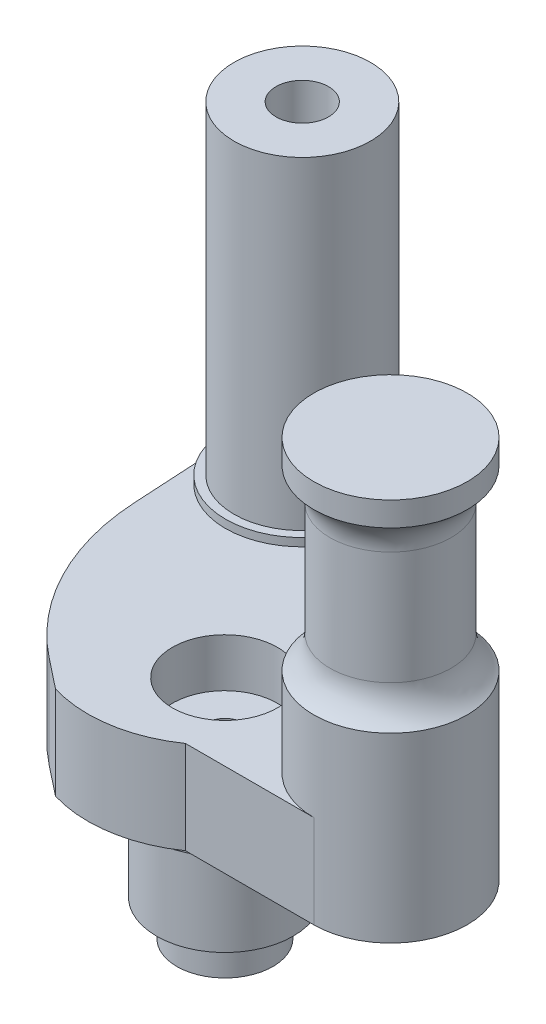
SolidWorks part; units mm, degrees
ref_plane "Спереди" through (0, 0, 0) normal (0, 0, 1) x (1, 0, 0)
ref_plane "Сверху" through (0, 0, 0) normal (0, 1, 0) x (1, 0, 0)
ref_plane "Справа" through (0, 0, 0) normal (1, 0, 0) x (0, 0, -1)
sketch "Эскиз1" plane through (0, 0, 0) normal (0, 1, 0) x (1, 0, 0)
  circle A0 centre (0, 0) radius 5.95
  dimension "D1" = 11.9
extrude "Бобышка-Вытянуть1" add sketch "Эскиз1" along normal blind 4.5
sketch "Эскиз4" plane through (0, 4.5, 0) normal (0, 1, 0) x (1, 0, 0)
  circle A0 centre (0, 0) radius 8.45
  dimension "D1" = 16.9
extrude "Бобышка-Вытянуть4" add sketch "Эскиз4" along normal blind 17.75
sketch "Эскиз6" plane through (0, 22.25, 0) normal (0, 1, 0) x (1, 0, 0)
  line L5 (0, 0) -> (0, 9.5) construction
  line L54 (0, 0) -> (0, -9.5) construction
  line L55 (0, -9.5) -> (-0.8337, -9.5)
  line L56 (-28.1148, 31.1924) -> (-19.0669, 6.3335)
  line L57 (-10.2606, 37.6908) -> (-28.1148, 31.1924)
  line L58 (-2.3949, 16.0798) -> (-10.2606, 37.6908)
  line L59 (30, -9.5) -> (0, -9.5)
  line L60 (30, 9.5) -> (30, -9.5)
  line L61 (7.0021, 9.5) -> (30, 9.5)
  arc A6 (-5.6703, -8.2525) -> (-0.8337, -9.5) centre (-0.8337, 0.5) ccw
  arc A7 (-5.6703, -8.2525) -> (-19.0669, 6.3335) centre (9.4167, 19.0492) cw
  arc A8 (-2.3949, 16.0798) -> (7.0021, 9.5) centre (7.0021, 19.5) ccw
extrude "Бобышка-Вытянуть6" add sketch "Эскиз6" along normal blind 5.75 and the other way blind 5.75
sketch "Эскиз12" plane through (0, 28, 0) normal (0, 1, 0) x (1, 0, 0)
  line L0 (-19.1877, 34.4416) -> (-15.9385, 25.5145) construction
  line L5 (-10.2606, 37.6908) -> (-28.1148, 31.1924) construction
  line L6 (-2.3949, 16.0798) -> (-10.2606, 37.6908) construction
  circle A0 centre (-15.9385, 25.5145) radius 9.5
  dimension "D1" = 19
  dimension "D2" = 9.5
extrude "Бобышка-Вытянуть10" add sketch "Эскиз12" along normal blind 1
sketch "Эскиз7" plane through (0, 0, 0) normal (0, -1, 0) x (1, 0, 0)
  circle A0 centre (0, 0) radius 2.3
  dimension "D1" = 4.6
extrude "Вырез-Вытянуть1" cut sketch "Эскиз7" against normal through all
sketch "Эскиз8" plane through (0, 28, 0) normal (0, 1, 0) x (1, 0, 0)
  circle A0 centre (0, 0) radius 6.5
  dimension "D1" = 13
extrude "Вырез-Вытянуть2" cut sketch "Эскиз8" against normal blind 6
sketch "Эскиз9" plane through (0, 28, 0) normal (0, -1, 0) x (1, 0, 0)
  line L0 (30, 0) -> (20.5, 0) construction
  line L3 (-0.8337, 9.5) -> (30, 9.5) construction
  circle A1 centre (20.5, 0) radius 9.5
  dimension "D1" = 19
  dimension "D2" = 9.5
extrude "Бобышка-Вытянуть7" add sketch "Эскиз9" against normal blind 36 from surface starting at face at (-11.7613, 28, -34.4726)
sketch "Эскиз10" plane through (0, 29, 0) normal (0, 1, 0) x (1, 0, 0)
  circle A1 centre (-15.9385, 25.5145) radius 8.45
  dimension "D1" = 16.9
extrude "Бобышка-Вытянуть8" add sketch "Эскиз10" along normal blind 40
sketch "Эскиз13" plane through (0, 16.5, 0) normal (0, -1, 0) x (1, 0, 0)
  circle A0 centre (0, 0) radius 9.5
  circle A1 centre (0, 0) radius 2.3
extrude "Бобышка-Вытянуть11" add sketch "Эскиз13" along normal blind 1
sketch "Эскиз14" plane through (0, 69, 0) normal (0, 1, 0) x (1, 0, 0)
  circle A0 centre (-15.9385, 25.5145) radius 3.25
  dimension "D1" = 6.5
extrude "Вырез-Вытянуть3" cut sketch "Эскиз14" against normal blind 8
sketch "Эскиз15" plane through (0, 28, 0) normal (0, 1, 0) x (1, 0, 0)
  line L39 (-24.8656, 22.2653) -> (-35.3362, 21.1554)
  line L40 (-35.3362, 21.1554) -> (-35.3362, 37.0401)
  line L41 (-35.3362, 37.0401) -> (1.9138, 42.4279)
  line L42 (1.9138, 42.4279) -> (-7.0114, 28.7637)
  line L43 (20.5, 9.5) -> (21.5142, 16.6037)
  line L44 (21.5142, 16.6037) -> (46.3919, 13.0518)
  line L45 (46.3919, 13.0518) -> (43.4369, -14.7941)
  line L46 (43.4369, -14.7941) -> (20.5, -14.2368)
  line L47 (20.5, -14.2368) -> (20.5, -9.5)
  arc A8 (-7.0114, 28.7637) -> (-24.8656, 22.2653) centre (-15.9385, 25.5145) ccw
  arc A9 (20.5, -9.5) -> (20.5, 9.5) centre (20.5, 0) ccw
extrude "Вырез-Вытянуть4" cut sketch "Эскиз15" against normal blind 18
sketch "Эскиз16" plane through (0, 28, 0) normal (0, 1, 0) x (1, 0, 0)
  circle A0 centre (20.5, 0) radius 7.5
  circle A1 centre (20.5, 0) radius 14.9564
  dimension "D1" = 15
extrude "Вырез-Вытянуть5" cut sketch "Эскиз16" along normal blind 22 from offset 11
fillet "Скругление2" radius 5 2 edges at (20.5, 39, 7.5) (20.5, 61, 7.5)
sketch "Эскиз17" plane through (0, 28, 0) normal (0, 1, 0) x (1, 0, 0)
  line L0 (0, 0) -> (-14.1086, 11.4909) construction
  line L1 (-9.2785, -11.6909) -> (-12.9726, -8.7754)
  line L2 (9.3719, 11.8075) -> (-5.4135, 23.4765)
  line L3 (-24.3377, 13.057) -> (-24.8656, 22.2653)
  line L4 (-5.4135, 23.4765) -> (-24.8656, 22.2653)
  circle A1 centre (0, 0) radius 7.5
  arc A3 (-9.2785, -11.6909) -> (9.3719, 11.8075) centre (-4.5907, 3.7389) ccw
  arc A4 (-12.9726, -8.7754) -> (-24.3377, 13.057) centre (5.6131, 14.774) cw
  point P4 (-7.0543, 5.7455)
  dimension "D1" = 30
  dimension "D2" = 30
extrude "Бобышка-Вытянуть12" add sketch "Эскиз17" against normal up to surface (11.5 mm away) up to face at (-0.7177, 16.5, -6.4761)
